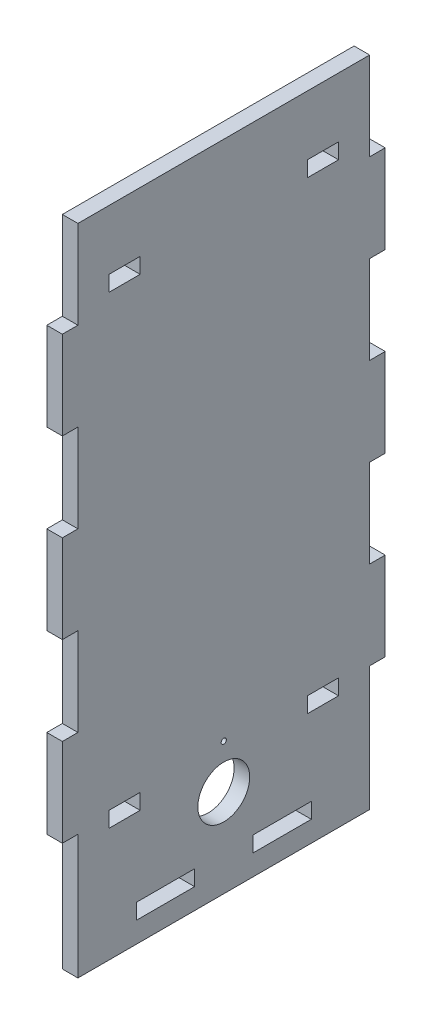
SolidWorks part; units mm, degrees
ref_plane "Front Plane" through (0, 0, 0) normal (0, 0, 1) x (1, 0, 0)
ref_plane "Top Plane" through (0, 0, 0) normal (0, 1, 0) x (1, 0, 0)
ref_plane "Right Plane" through (0, 0, 0) normal (1, 0, 0) x (0, 0, -1)
sketch "Sketch1" plane through (0, 0, 0) normal (1, 0, 0) x (0, 0, -1)
  line L1 (-56.25, -119) -> (56.25, -119)
  line L2 (-56.25, -119) -> (-56.25, 119)
  line L3 (-56.25, 119) -> (56.25, 119)
  line L4 (56.25, -119) -> (56.25, 119)
  line L5 (-56.25, -119) -> (56.25, 119) construction
  line L6 (-56.25, 119) -> (56.25, -119) construction
  point P0 (0, 0)
  dimension "D1" = 238
  dimension "D2" = 112.5
extrude "Boss-Extrude1" add sketch "Sketch1" along normal blind 6
sketch "Sketch2" plane through (6, 0, 0) normal (1, 0, 0) x (0, 0, -1)
  line L0 (0, -119) -> (0, -99) construction
  line L1 (0, -82.0294) -> (30.9706, -113) construction
  line L4 (56.25, -119) -> (56.25, 119)
  line L5 (56.25, 119) -> (-56.25, 119)
  line L6 (-56.25, 119) -> (-56.25, -119)
  line L7 (-56.25, -119) -> (56.25, -119)
  line L8 (56.25, -119) -> (56.25, 119) construction
  line L9 (56.25, 119) -> (-56.25, 119) construction
  line L10 (-56.25, 119) -> (-56.25, -119) construction
  line L11 (-56.25, -119) -> (56.25, -119) construction
  line L12 (0, -99) -> (0, -82.0294) construction
  line L13 (30.9706, -113) -> (0, -113) construction
  line L14 (0, -82.0294) -> (30.9706, -82.0294) construction
  line L15 (30.9706, -82.0294) -> (30.9706, -113) construction
  line L16 (0, -113) -> (0, -109) construction
  line L17 (8.4853, -90.5147) -> (7.0711, -91.9289) construction
  line L18 (0, -82.0294) -> (-16.9706, -82.0294) construction
  line L19 (-16.9706, -82.0294) -> (0, -65.0589) construction
  line L20 (0, -65.0589) -> (0, -82.0294) construction
  line L21 (0, -65.0589) -> (16.9706, -82.0294) construction
  line L22 (16.9706, -82.0294) -> (0, -99) construction
  line L23 (0, -99) -> (-16.9706, -82.0294) construction
  line L24 (-16.9706, -74.0294) -> (-16.9706, -90.0294) construction
  line L25 (-13.4706, -74.0294) -> (-13.4706, -90.0294)
  line L26 (-20.4706, -74.0294) -> (-20.4706, -90.0294)
  line L27 (0, -65.0589) -> (0, -60.5589) construction
  line L28 (0, -60.5589) -> (-4.5, -60.5589) construction
  line L29 (-4.5, -60.5589) -> (-4.5, -65.0589) construction
  circle A2 centre (0, -82.0294) radius 30.9706
  circle A3 centre (0, -99) radius 10
  circle A4 centre (-16.9706, -82.0294) radius 10 construction
  circle A5 centre (0, -65.0589) radius 10 construction
  arc A7 (-13.4706, -74.0294) -> (-20.4706, -74.0294) centre (-16.9706, -74.0294) ccw
  arc A8 (-20.4706, -90.0294) -> (-13.4706, -90.0294) centre (-16.9706, -90.0294) ccw
  circle A10 centre (-4.5, -60.5589) radius 1.4
  circle A11 centre (0, -60.5589) radius 1.4
  circle A12 centre (4.5, -60.5589) radius 1.4
  circle A15 centre (0, -65.0589) radius 1.4
  circle A16 centre (4.5, -65.0589) radius 1.4
  circle A19 centre (0, -69.5589) radius 1.4
  circle A20 centre (4.5, -69.5589) radius 1.4
  circle A31 centre (-4.5, -65.0589) radius 1.4
  circle A32 centre (-4.5, -69.5589) radius 1.4
  circle A35 centre (0, -82.0294) radius 1
  point P19 (-16.9706, -82.0294)
  dimension "D2" = 20
  dimension "D8" = 2.8
  dimension "D12" = 4.5
  dimension "D14" = 2
  dimension "D3" = 6
  dimension "D4" = 2
  dimension "D5" = 4
  dimension "D6" = 7
  dimension "D7" = 16
  dimension "D9" = 4.5
  dimension "D13" = 4.5
  dimension "D1" = 0
  dimension "D10" = 3
  dimension "D11" = 3
extrude "Cut-Extrude1" cut sketch "Sketch2" against normal blind 6 contours A3 | A35 region at (6, -99, 0) region at (6, -82.0294, 0)
sketch "Sketch3" plane through (6, 0, 0) normal (1, 0, 0) x (0, 0, -1)
  line L0 (-56.25, 119) -> (-56.25, -119) construction
  line L2 (-56.25, -89) -> (-56.25, -83) construction
  line L3 (-56.25, -83) -> (56.25, -83) construction
  line L4 (56.25, -89) -> (56.25, -83) construction
  line L5 (56.25, -119) -> (56.25, 119) construction
  line L6 (-44.25, -89) -> (-56.25, -89) construction
  line L7 (-44.25, -83) -> (-32.25, -83)
  line L8 (-44.25, -83) -> (-44.25, -89)
  line L9 (-44.25, -89) -> (-32.25, -89)
  line L10 (-32.25, -83) -> (-32.25, -89)
  line L11 (32.25, -89) -> (44.25, -89)
  line L12 (32.25, -89) -> (32.25, -83)
  line L13 (32.25, -83) -> (44.25, -83)
  line L14 (44.25, -89) -> (44.25, -83)
  line L15 (-32.25, -89) -> (32.25, -89)
  line L16 (44.25, -89) -> (56.25, -89)
  line L17 (-56.25, -119) -> (56.25, -119) construction
  dimension "D1" = 6
  dimension "D2" = 12
  dimension "D3" = 12
  dimension "D4" = 36
extrude "Cut-Extrude2" cut sketch "Sketch3" against normal blind 6 contours L10 L7 L8 L9 | L11 L14 L13 L12 region at (6, -86, -38.25) region at (6, -86, 38.25)
sketch "Sketch4" plane through (0, -119, 0) normal (0, -1, 0) x (1, 0, 0)
  line L0 (6, 56.25) -> (6, -56.25) construction
  line L1 (0, -56.25) -> (6, -56.25)
  line L2 (0, -56.25) -> (0, -33.75)
  line L3 (0, -33.75) -> (6, -33.75)
  line L4 (6, -56.25) -> (6, -33.75)
  line L5 (0, 56.25) -> (0, -56.25) construction
  line L6 (6, -33.75) -> (0, -33.75) construction
  line L7 (6, -33.75) -> (6, -11.25) construction
  line L8 (6, -11.25) -> (0, -11.25) construction
  line L9 (0, -33.75) -> (0, -11.25) construction
  line L11 (6, 11.25) -> (0, 11.25)
  line L12 (6, 11.25) -> (6, -11.25)
  line L13 (6, -11.25) -> (0, -11.25)
  line L14 (0, 11.25) -> (0, -11.25)
  line L15 (0, 11.25) -> (6, 11.25) construction
  line L16 (0, 11.25) -> (0, 33.75) construction
  line L17 (0, 33.75) -> (6, 33.75) construction
  line L18 (6, 11.25) -> (6, 33.75) construction
  line L19 (6, 33.75) -> (0, 33.75)
  line L20 (6, 33.75) -> (6, 56.25)
  line L21 (6, 56.25) -> (0, 56.25)
  line L22 (0, 33.75) -> (0, 56.25)
extrude "Boss-Extrude2" add sketch "Sketch4" along normal blind 6
sketch "Sketch5" plane through (6, 0, 0) normal (1, 0, 0) x (0, 0, -1)
  line L0 (56.25, 90) -> (44.25, 90) construction
  line L1 (-32.25, 90) -> (-44.25, 90)
  line L2 (-32.25, 90) -> (-32.25, 96)
  line L3 (-32.25, 96) -> (-44.25, 96)
  line L4 (-44.25, 90) -> (-44.25, 96)
  line L5 (56.25, 96) -> (44.25, 96) construction
  line L6 (-32.25, 90) -> (-32.25, -83) construction
  line L7 (44.25, 90) -> (32.25, 90)
  line L8 (44.25, 90) -> (44.25, 96)
  line L9 (44.25, 96) -> (32.25, 96)
  line L10 (32.25, 90) -> (32.25, 96)
  line L11 (-44.25, 90) -> (-44.25, -83)
  line L12 (-44.25, 90) -> (44.25, 90)
  line L13 (0, 90) -> (0, 0)
  line L22 (56.25, -125) -> (56.25, 119)
  line L23 (56.25, 119) -> (-56.25, 119)
  line L24 (-56.25, 119) -> (-56.25, -125)
  line L25 (-56.25, -125) -> (-33.75, -125)
  line L26 (-33.75, -125) -> (-33.75, -119)
  line L27 (-33.75, -119) -> (-11.25, -119)
  line L28 (-11.25, -119) -> (-11.25, -125)
  line L29 (-11.25, -125) -> (11.25, -125)
  line L30 (11.25, -125) -> (11.25, -119)
  line L31 (11.25, -119) -> (33.75, -119)
  line L32 (33.75, -119) -> (33.75, -125)
  line L33 (33.75, -125) -> (56.25, -125)
  line L34 (56.25, -125) -> (56.25, 119)
  line L35 (56.25, 119) -> (-56.25, 119)
  line L36 (-56.25, 119) -> (-56.25, -125)
  line L37 (-56.25, -125) -> (-33.75, -125)
  line L38 (-33.75, -125) -> (-33.75, -119)
  line L39 (-33.75, -119) -> (-11.25, -119)
  line L40 (-11.25, -119) -> (-11.25, -125)
  line L41 (-11.25, -125) -> (11.25, -125)
  line L42 (11.25, -125) -> (11.25, -119)
  line L43 (11.25, -119) -> (33.75, -119)
  line L44 (33.75, -119) -> (33.75, -125)
  line L45 (33.75, -125) -> (56.25, -125)
  point P14 (-32.25, -83)
  dimension "D1" = 0
extrude "Cut-Extrude3" cut sketch "Sketch5" against normal blind 6 contours L4 L1 L2 L3 | L10 L7 L8 L9 region at (6, 93, 38.25) region at (6, 93, -38.25)
sketch "Sketch6" plane through (0, 0, -56.25) normal (0, 0, -1) x (-1, 0, 0)
  line L33 (-6, -125) -> (-6, 119) construction
  line L34 (0, 119) -> (-6, 119)
  line L35 (0, 119) -> (0, 85)
  line L36 (0, 85) -> (-6, 85)
  line L37 (-6, 119) -> (-6, 85)
  line L38 (0, -125) -> (0, 119) construction
  line L39 (-6, 85) -> (0, 85)
  line L40 (-6, 85) -> (-6, 51)
  line L41 (-6, 51) -> (0, 51)
  line L42 (0, 85) -> (0, 51)
  line L43 (0, -125) -> (-6, -125) construction
  line L44 (0, 51) -> (-6, 51)
  line L45 (0, 51) -> (0, 17)
  line L46 (0, 17) -> (-6, 17)
  line L47 (-6, 51) -> (-6, 17)
  line L48 (-6, 17) -> (0, 17)
  line L49 (-6, 17) -> (-6, -17)
  line L50 (-6, -17) -> (0, -17)
  line L51 (0, 17) -> (0, -17)
  line L52 (0, -17) -> (-6, -17)
  line L53 (0, -17) -> (0, -51)
  line L54 (0, -51) -> (-6, -51)
  line L55 (-6, -17) -> (-6, -51)
  line L56 (-6, -51) -> (0, -51)
  line L57 (-6, -51) -> (-6, -85)
  line L58 (-6, -85) -> (0, -85)
  line L59 (0, -51) -> (0, -85)
  line L60 (0, -85) -> (-6, -85)
  line L61 (0, -85) -> (0, -119)
  line L62 (0, -119) -> (-6, -119)
  line L63 (-6, -85) -> (-6, -119)
  line L64 (-6, -119) -> (0, -119)
  line L65 (-6, -119) -> (-6, -125)
  line L66 (-6, -125) -> (0, -125) construction
  line L67 (0, -119) -> (0, -125) construction
  line L68 (0, -125) -> (-6, -125)
  point P23 (0, -105.6137)
  point P24 (0, 0)
  point P25 (0, -125)
  point P26 (0, -121.894)
  line M15 (0, -125) -> (0, 119)
  line M17 (-6, 119) -> (-6, -125)
extrude "Boss-Extrude3" add sketch "Sketch6" along normal blind 6 contours M17 M15 | M17 M15 | M17 M15 region at (3, 68, -56.25) region at (3, 0, -56.25) region at (3, -68, -56.25)
mirror "Mirror1" about plane through (0, 0, 0) normal (0, 0, 1) of "Boss-Extrude3"
sketch "Sketch7" plane through (0, -125, 0) normal (0, -1, 0) x (-1, 0, 0)
  line L1 (0, 56.25) -> (-6, 56.25)
  line L2 (0, 56.25) -> (0, -56.25)
  line L3 (0, -56.25) -> (-6, -56.25)
  line L4 (-6, 56.25) -> (-6, -56.25)
extrude "Boss-Extrude4" add sketch "Sketch7" along normal blind 8
